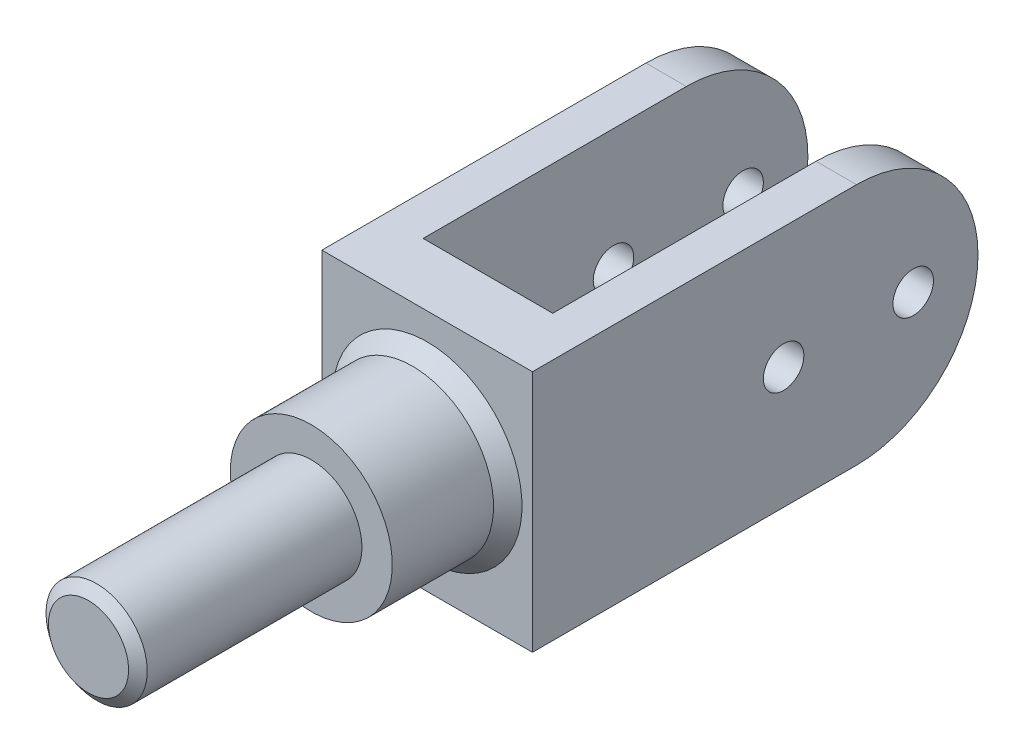
SolidWorks part; units mm, degrees
ref_plane "Front Plane" through (0, 0, 0) normal (0, 0, 1) x (1, 0, 0)
ref_plane "Top Plane" through (0, 0, 0) normal (0, 1, 0) x (1, 0, 0)
ref_plane "Right Plane" through (0, 0, 0) normal (1, 0, 0) x (0, 0, -1)
sketch "Sketch2" plane through (0, 0, 0) normal (1, 0, 0) x (0, 0, -1)
  line L1 (15.055, -7.6861) -> (-68.645, -7.6861)
  line L2 (-68.645, -7.6861) -> (-68.645, 2.203)
  line L3 (-66.645, 4.8139) -> (-13.645, 4.8139)
  line L4 (-13.645, 4.8139) -> (-13.645, 12.3139)
  line L5 (-13.645, 12.3139) -> (11.355, 12.3139)
  line L8 (-68.645, 2.203) -> (-66.645, 4.8139)
  line L9 (15.055, -7.6861) -> (15.055, 15.8068)
  line L10 (11.355, 12.3139) -> (15.055, 15.8068)
  line L11 (11.355, 12.3139) -> (11.355, 15.8068) construction
  line L12 (11.355, 12.3139) -> (11.355, -7.6861) construction
  line L13 (11.355, 15.8068) -> (-68.645, 15.8068) construction
  line L14 (-68.645, 2.203) -> (-68.645, 15.8068) construction
  line L15 (11.355, 15.8068) -> (15.055, 15.8068) construction
  line L16 (-66.645, 4.8139) -> (-68.645, 4.8139) construction
revolve "Revolve2" add sketch "Sketch2" angle 360 about L1
sketch3d "3DSketch2"
  line L0 (26.0012, 22.3218, -19.9659) -> (-25.9988, 22.3218, -19.9659)
  line L2 (26.0012, -37.6782, -19.9659) -> (-25.9988, -37.6782, -19.9659)
  line L13 (-25.9988, -37.6782, -19.9659) -> (-25.9988, 22.3218, -19.9659)
  line L15 (26.0012, 22.3218, -19.9659) -> (26.0012, -37.6782, -19.9659)
extrude "Boss-Extrude1" add sketch "3DSketch2" along direction (0, 0, 1) on the side of the normal blind 5 and the other way blind 105
sketch "Sketch5" plane through (0, 22.3218, 0) normal (0, 1, 0) x (1, 0, 0)
  line L1 (-25.9988, 124.9659) -> (26.0012, 124.9659) construction
  line L3 (-15.9988, 124.9659) -> (-15.9988, 29.9659)
  line L4 (-15.9988, 29.9659) -> (16.0012, 29.9659)
  line L5 (16.0012, 29.9659) -> (16.0012, 124.9659)
  line L9 (-15.9988, 124.9659) -> (16.0012, 124.9659)
extrude "Cut-Extrude1" cut sketch "Sketch5" against normal blind 100
sketch "Sketch7" plane through (26.0012, 0, 0) normal (1, 0, 0) x (0, 0, -1)
  line L0 (14.9659, -37.6782) -> (108.9659, -37.6782) construction
  line L1 (14.9659, -37.6782) -> (124.9659, -37.6782) construction
  line L2 (108.9659, -37.6782) -> (108.9659, -7.6782) construction
  line L3 (108.9659, -7.6782) -> (76.9659, -7.6782) construction
  circle A0 centre (76.9659, -7.6782) radius 5
  circle A1 centre (108.9659, -7.6782) radius 5
extrude "Cut-Extrude2" cut sketch "Sketch7" against normal blind 113 and the other way blind 40
sketch "Sketch8" plane through (26.0012, 0, 0) normal (1, 0, 0) x (0, 0, -1)
  line L0 (124.9659, 22.3218) -> (124.9659, -37.6782)
  line L1 (14.9659, -37.6782) -> (124.9659, -37.6782) construction
  line L2 (124.9659, -37.6782) -> (94.9659, -37.6782)
  line L5 (94.9659, 22.3218) -> (124.9659, 22.3218) construction
  arc A0 (94.9659, -37.6782) -> (94.9659, 22.3218) centre (94.9659, -7.6782) ccw
  line M6 (124.9659, -37.6782) -> (124.9659, 22.3218)
  line M7 (124.9659, 22.3218) -> (14.9659, 22.3218)
  line M9 (14.9659, -37.6782) -> (124.9659, -37.6782)
extrude "Cut-Extrude4" cut sketch "Sketch8" against normal blind 234 and the other way blind 234 contours A0 L0 M7 | A0 M9 M6 region at (26.0012, -30.9771, -118.2648) region at (26.0012, 15.6208, -118.2648)
